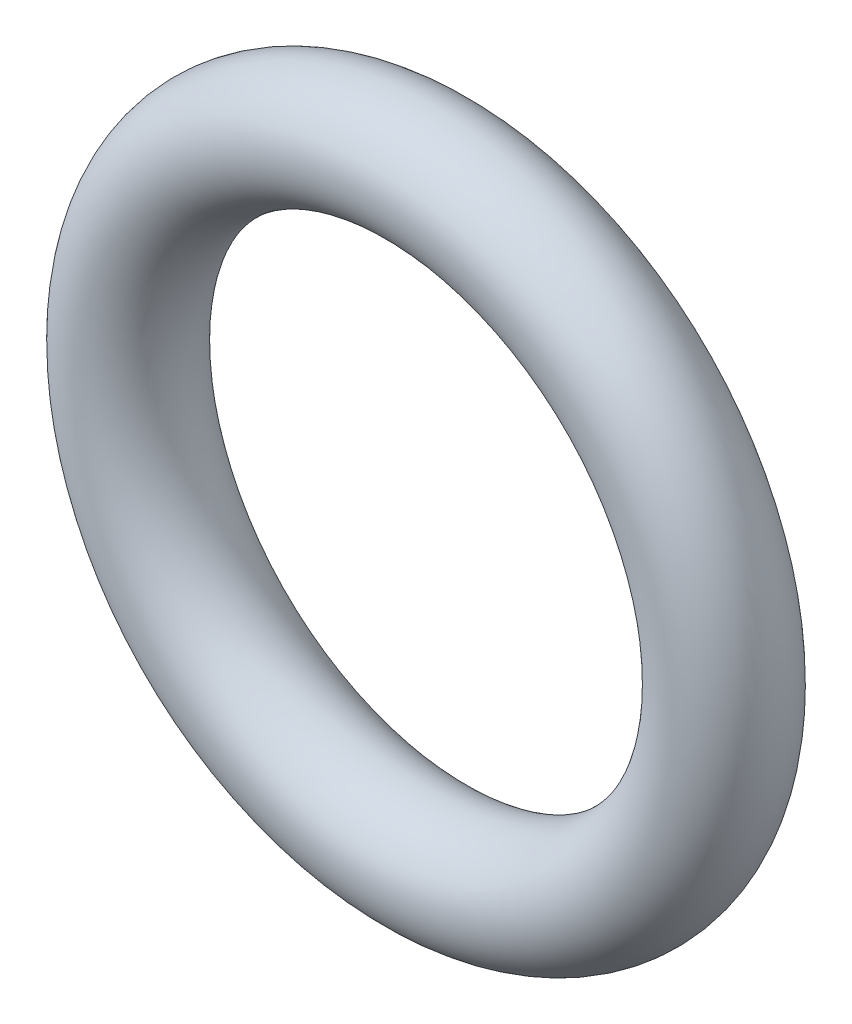
SolidWorks part; units mm, degrees
ref_plane "Front" through (0, 0, 0) normal (0, 0, 1) x (1, 0, 0)
ref_plane "Top" through (0, 0, 0) normal (0, 1, 0) x (1, 0, 0)
ref_plane "Right" through (0, 0, 0) normal (1, 0, 0) x (0, 0, -1)
sketch "Sketch1" plane through (0, 0, 0) normal (0, 0, 1) x (1, 0, 0)
  circle A0 centre (0, 0) radius 3.75
  dimension "d1" = 7.5
sketch "Sketch2" plane through (0, 0, 0) normal (0, 1, 0) x (1, 0, 0)
  circle A0 centre (-4.65, 0) radius 0.9
  point P2 (-3.75, 0)
  dimension "d2" = 1.8
sweep "Sweep1" add profiles "Sketch2" path "Sketch1"
ref_axis "Axis1" through (0, 0, -5.0345) along (0, 0, 1)
